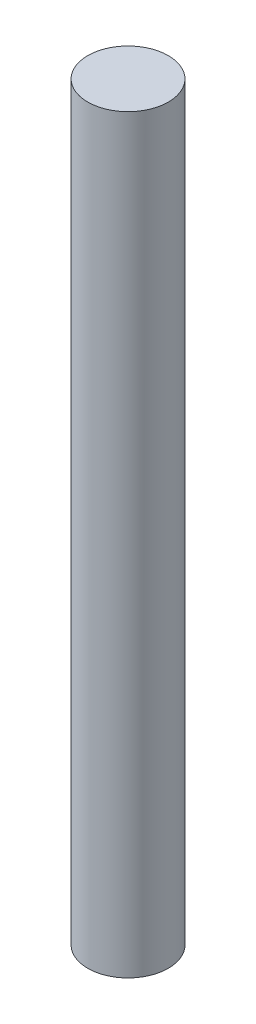
SolidWorks part; units mm, degrees
ref_plane "Спереди" through (0, 0, 0) normal (0, 0, 1) x (1, 0, 0)
ref_plane "Сверху" through (0, 0, 0) normal (0, 1, 0) x (1, 0, 0)
ref_plane "Справа" through (0, 0, 0) normal (1, 0, 0) x (0, 0, -1)
sketch "Эскиз2" plane through (0, 0, 0) normal (0, 1, 0) x (1, 0, 0)
  circle A0 centre (0, 0) radius 35
  circle A1 centre (0, 0) radius 34
  dimension "D1" = 70
  dimension "D2" = 68
extrude "Бобышка-Вытянуть1" add sketch "Эскиз2" along normal blind 650
sketch "Эскиз3" plane through (0, 0, 0) normal (0, -1, 0) x (1, 0, 0)
  circle A0 centre (0, 0) radius 35
extrude "Бобышка-Вытянуть2" add sketch "Эскиз3" along normal blind 1
sketch "Эскиз4" plane through (0, 650, 0) normal (0, 1, 0) x (1, 0, 0)
  circle A0 centre (0, 0) radius 35
extrude "Бобышка-Вытянуть3" add sketch "Эскиз4" along normal blind 1
sketch "Эскиз5" plane through (0, 0, 0) normal (1, 0, 0) x (0, 0, -1)
  line L0 (-35, -1) -> (35, -1) construction
  circle A0 centre (0, 14.25) radius 0.25
  point P2 (0, 56.3636)
  point P3 (0, 45.6823)
  dimension "D1" = 0.5
  dimension "D2" = 15
